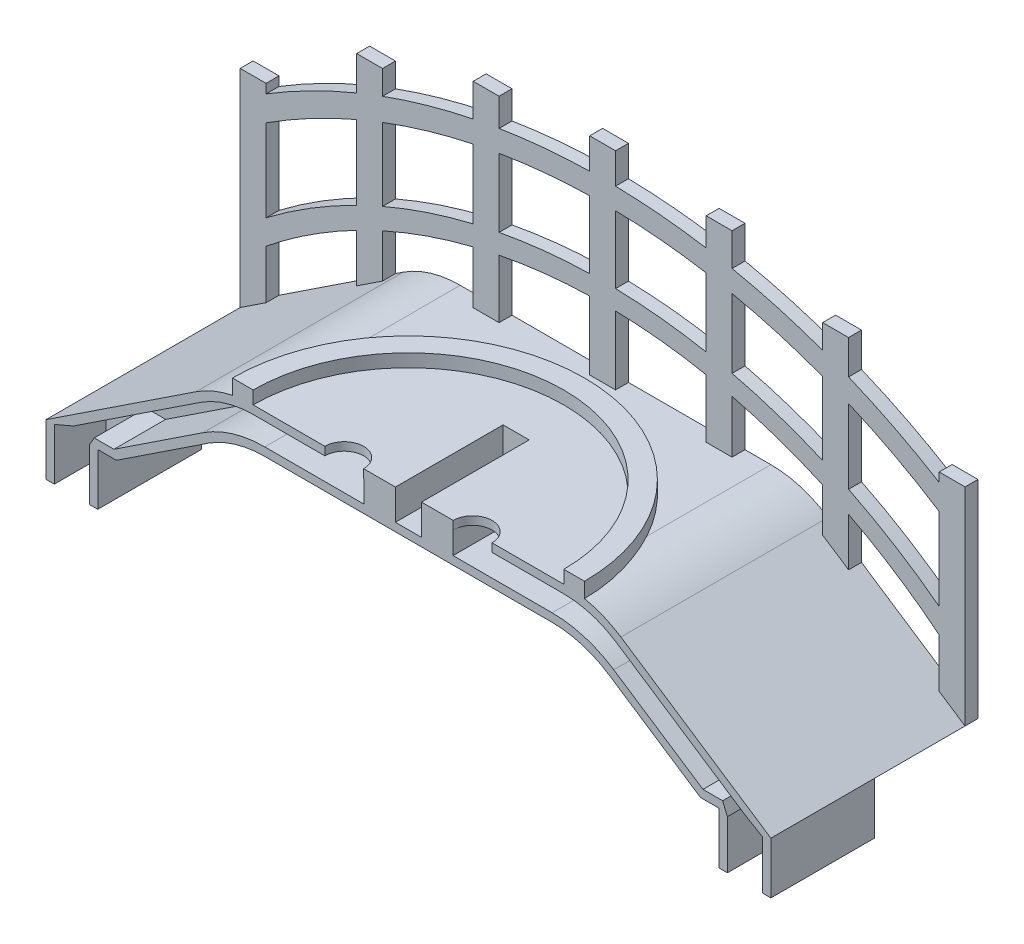
SolidWorks part; units mm, degrees
ref_plane "Front Plane" through (0, 0, 0) normal (0, 0, 1) x (1, 0, 0)
ref_plane "Top Plane" through (0, 0, 0) normal (0, 1, 0) x (1, 0, 0)
ref_plane "Right Plane" through (0, 0, 0) normal (1, 0, 0) x (0, 0, -1)
sketch "Sketch5" plane through (0, 0, 0) normal (0, 0, 1) x (1, 0, 0)
  line L0 (1.3132, -1.9864) -> (9.914, 3.6997)
  line L1 (12.7, 7.134) -> (31.75, 7.134)
  line L2 (0, 0) -> (9.198, 6.081)
  line L3 (35.252, 6.081) -> (44.45, 0)
  line L4 (0, 0) -> (10.7907, 0) construction
  line L5 (44.45, 0) -> (33.6593, 0) construction
  line L6 (13.416, 4.7527) -> (31.034, 4.7527)
  line L7 (34.536, 3.6997) -> (43.1368, -1.9864)
  line L8 (0, 0) -> (4.3178, 0)
  line L9 (44.45, 0) -> (40.1322, 0)
  line L10 (0, 0) -> (0, 9.525)
  line L11 (44.45, 0) -> (44.45, 9.525)
  line L12 (22.225, 7.134) -> (22.225, 16.659) construction
  line L13 (22.225, 7.134) -> (22.225, 3.959) construction
  line L14 (0, 0) -> (1.5875, 0)
  line L15 (0, 0) -> (0, 12.7)
  line L16 (0, 12.7) -> (1.5875, 12.7)
  line L17 (1.5875, 0) -> (1.5875, 12.7)
  line L18 (23.0187, 3.959) -> (21.4312, 3.959)
  line L19 (23.0187, 3.959) -> (23.0188, 19.834)
  line L20 (23.0188, 19.834) -> (21.4312, 19.834)
  line L21 (21.4312, 3.959) -> (21.4312, 19.834)
  line L22 (1.5875, 9.2118) -> (7.1438, 9.2118) construction
  line L23 (7.1437, 17.0604) -> (8.7312, 17.0604)
  line L24 (7.1437, 17.0604) -> (7.1438, 1.1854)
  line L25 (7.1438, 1.1854) -> (8.7313, 1.1854)
  line L26 (8.7312, 17.0604) -> (8.7313, 1.1854)
  line L27 (14.2875, 19.1598) -> (15.875, 19.1598)
  line L28 (14.2875, 19.1598) -> (14.2875, 3.2848)
  line L29 (14.2875, 3.2848) -> (15.875, 3.2848)
  line L30 (15.875, 19.1598) -> (15.875, 3.2848)
  line L31 (8.7313, 8.208) -> (14.2875, 8.208) construction
  line L32 (15.875, 13.1596) -> (21.4312, 13.1596) construction
  line L33 (7.9375, 17.0604) -> (7.9375, 13.8854) construction
  line L34 (15.0812, 19.1598) -> (15.0812, 15.9848) construction
  line L35 (44.45, 0) -> (40.1322, 0)
  line L36 (30.1625, 19.1598) -> (28.575, 19.1598)
  line L37 (30.1625, 19.1598) -> (30.1625, 3.2848)
  line L38 (28.575, 19.1598) -> (28.575, 3.2848)
  line L39 (30.1625, 3.2848) -> (28.575, 3.2848)
  line L40 (37.3062, 1.1854) -> (35.7187, 1.1854)
  line L41 (37.3062, 17.0604) -> (35.7187, 17.0604)
  line L42 (35.7187, 17.0604) -> (35.7187, 1.1854)
  line L43 (37.3062, 17.0604) -> (37.3062, 1.1854)
  line L44 (44.45, 12.7) -> (42.8625, 12.7)
  line L45 (44.45, 0) -> (44.45, 12.7)
  line L46 (44.45, 0) -> (44.45, 9.525)
  line L47 (42.8625, 0) -> (42.8625, 12.7)
  line L48 (11.5067, 4.7527) -> (32.9433, 4.7527) construction
  line L49 (32.9433, 4.7527) -> (43.1368, -1.9864) construction
  line L50 (10.7907, 7.134) -> (33.6593, 7.134) construction
  line L51 (33.6593, 7.134) -> (44.45, 0) construction
  line L52 (1.3132, -1.9864) -> (11.5067, 4.7527) construction
  line L53 (0, 0) -> (10.7907, 7.134) construction
  arc A0 (0, 9.525) -> (44.45, 9.525) centre (22.225, -21.5277) cw
  arc A1 (0, 11.1125) -> (44.45, 11.1125) centre (22.225, -21.5277) cw
  arc A2 (31.034, 4.7527) -> (34.536, 3.6997) centre (31.034, -1.5973) cw
  arc A3 (31.75, 7.134) -> (35.252, 6.081) centre (31.75, 0.784) cw
  arc A4 (9.914, 3.6997) -> (13.416, 4.7527) centre (13.416, -1.5973) cw
  arc A5 (12.7, 7.134) -> (9.198, 6.081) centre (12.7, 0.784) ccw
  point P65 (33.6593, 7.134)
  dimension "D12" = 6.35
  dimension "D2" = 19.05
  dimension "D1" = 44.45
  dimension "D3" = 2.3813
  dimension "D4" = 9.525
  dimension "D5" = 1.5875
  dimension "D6" = 12.7
  dimension "D7" = 1.5875
  dimension "D8" = 15.875
  dimension "D9" = 12.7
  dimension "D10" = 3.175
  dimension "D11" = 1.5875
extrude "Boss-Extrude1" add sketch "Sketch5" along normal blind 12.7 contours L25 L24 L2 L17 L8 L0 | L8 L17 L2 | L26 L2 L24 L25 L0 | L28 A5 L2 L26 L0 A4 | L1 A5 L28 A4 L6 L30 | L1 L30 L6 L21 | L21 L6 L19 L1 | L38 L1 L19 L6 | A3 L1 L38 L6 A2 L37 | A3 L37 A2 L7 L42 L3 | L43 L3 L42 L7 L40 | L35 L47 L3 L43 L40 L7 | L47 L9 L3 region at (4.7092, 1.8379, 0) region at (7.9375, 3.8203, 0) region at (1.0583, 0.3498, 0) region at (11.4024, 5.4948, 0) region at (15.0812, 5.9433, 0) region at (18.6531, 5.9433, 0) region at (22.225, 5.9433, 0) region at (25.7969, 5.9433, 0) region at (29.3688, 5.9433, 0) region at (33.0476, 5.4948, 0) region at (36.5125, 3.8203, 0) region at (39.7408, 1.8379, 0) region at (43.3917, 0.3498, 0)
extrude "Boss-Extrude2" add sketch "Sketch5<4>" along normal blind 0.7937 separate body contours A1 L15 A0 L17 | A1 L17 A0 L24 | A1 L24 A0 L26 | A1 L26 A0 L28 | A1 L28 A0 L30 | A1 L30 A0 L21 | A1 L21 A0 L19 | A1 L19 A0 L38 | A1 L38 A0 L37 | A1 L37 A0 L42 | A1 L42 A0 L43 | A1 L43 A0 L47 | A1 L47 A0 L45 region at (4.3267, 12.8905, 0) region at (7.9352, 14.5811, 0) region at (0.7895, 10.851, 0) region at (11.4895, 15.7587, 0) region at (15.0802, 16.6439, 0) region at (18.647, 17.111, 0) region at (22.225, 17.3071, 0) region at (25.803, 17.111, 0) region at (29.3698, 16.6439, 0) region at (32.9605, 15.7587, 0) region at (36.5148, 14.5811, 0) region at (40.1233, 12.8905, 0) region at (43.6605, 10.851, 0)
sketch "Sketch5<4>" plane through (0, 0, 0) normal (0, 0, 1) x (1, 0, 0) same geometry as "Sketch5"
extrude "Boss-Extrude6" add sketch "Sketch5<7>" along normal blind 0.7937 contours L15 A1 L17 L16 | A0 L10 L2 L17 | A1 L15 A0 L17 | A0 L24 L2 L26 | L24 A1 L26 L23 | L26 L2 L24 L0 | L26 L0 L24 L25 | A1 L24 A0 L26 | L28 A1 L30 L27 | A1 L28 A0 L30 | A0 L28 L1 L30 | L30 L1 L28 L6 | L30 L6 L28 L29 | L21 L18 L19 L6 | L21 L6 L19 L1 | A0 L21 L1 L19 | L21 A1 L19 L20 | A1 L21 A0 L19 | L38 A1 L37 L36 | A0 L38 L1 L37 | L1 L38 L6 L37 | L39 L37 L6 L38 | L43 L7 L42 L40 | L43 L3 L42 L7 | A0 L42 L3 L43 | A1 L42 A0 L43 | L42 A1 L43 L41 | L47 A1 L45 L44 | A1 L47 A0 L45 | A0 L47 L3 L11 | L47 L9 L3 region at (7.9375, 3.8203, 0) region at (8.0525, 1.8272, 0) region at (7.9312, 9.5615, 0) region at (0.7941, 5.2992, 0) region at (7.9352, 14.5811, 0) region at (0.7895, 10.851, 0) region at (7.8917, 16.1623, 0) region at (0.6663, 12.1261, 0) region at (15.0812, 5.9433, 0) region at (15.0812, 4.0188, 0) region at (15.0858, 11.5584, 0) region at (15.0802, 16.6439, 0) region at (15.0604, 18.2312, 0) region at (22.225, 5.9433, 0) region at (22.225, 4.3558, 0) region at (22.225, 11.8951, 0) region at (22.225, 17.3071, 0) region at (22.225, 18.896, 0) region at (29.3688, 5.9433, 0) region at (29.3688, 4.0188, 0) region at (29.3642, 11.5584, 0) region at (29.3896, 18.2312, 0) region at (36.5188, 9.5615, 0) region at (36.5148, 14.5811, 0) region at (36.5583, 16.1623, 0) region at (36.5125, 3.8203, 0) region at (36.3975, 1.8272, 0) region at (43.6559, 5.2992, 0) region at (43.6605, 10.851, 0) region at (43.7837, 12.1261, 0) region at (43.3917, 0.3498, 0)
sketch "Sketch5<7>" plane through (0, 0, 0) normal (0, 0, 1) x (1, 0, 0) same geometry as "Sketch5"
sketch "Sketch6" plane through (0, 0, 0) normal (0, 0, -1) x (-1, 0, 0)
  line L0 (-44.45, 0) -> (-44.45, 12.7) construction
  line L1 (0, 0) -> (0, 12.7) construction
  line L2 (-44.45, 4.2704) -> (-44.45, 2.6829)
  line L3 (0, 2.6829) -> (0, 4.2704)
  arc A0 (-44.45, 4.2704) -> (0, 4.2704) centre (-22.225, -21.5277) cw
  arc A1 (-44.45, 2.6829) -> (0, 2.6829) centre (-22.225, -21.5277) cw
  arc A2 (-23.0187, 16.6507) -> (-28.575, 16.1273) centre (-22.225, -21.5277) ccw construction
  dimension "D1" = 1.5875
extrude "Boss-Extrude7" add sketch "Sketch6" against normal blind 0.7937
sketch "Sketch7" plane through (0, 0, 12.7) normal (0, 0, 1) x (1, 0, 0)
  line L0 (22.225, 7.134) -> (12.7, 7.134)
  line L1 (12.7, 7.134) -> (31.75, 7.134) construction
  line L2 (12.7, 7.134) -> (12.7, 6.626)
  line L3 (13.416, 4.7527) -> (31.034, 4.7527) construction
  line L4 (12.7, 6.626) -> (31.75, 6.626)
  line L5 (12.7, 6.626) -> (12.7, 5.2607)
  line L6 (12.7, 5.2607) -> (31.75, 5.2607)
  line L7 (31.75, 6.626) -> (31.75, 5.2607)
  line L20 (1.6895, 0.508) -> (4.1651, 0.508)
  line L21 (4.1651, 0.508) -> (9.6338, 4.1235)
  line L22 (9.4782, 5.6572) -> (1.6895, 0.508)
  line L23 (1.6895, 0.508) -> (4.1651, 0.508)
  line L24 (4.1651, 0.508) -> (9.6338, 4.1235)
  line L25 (9.4782, 5.6572) -> (1.6895, 0.508)
  line L37 (34.8162, 4.1235) -> (40.2849, 0.508)
  line L38 (40.2849, 0.508) -> (42.7605, 0.508)
  line L39 (42.7605, 0.508) -> (34.9718, 5.6572)
  line L40 (34.8162, 4.1235) -> (40.2849, 0.508)
  line L41 (40.2849, 0.508) -> (42.7605, 0.508)
  line L42 (42.7605, 0.508) -> (34.9718, 5.6572)
  arc A8 (13.416, 5.2607) -> (9.6338, 4.1235) centre (13.416, -1.5973) ccw
  arc A9 (12.7, 6.626) -> (9.4782, 5.6572) centre (12.7, 0.784) ccw
  arc A10 (13.416, 5.2607) -> (9.6338, 4.1235) centre (13.416, -1.5973) ccw
  arc A11 (12.7, 6.626) -> (9.4782, 5.6572) centre (12.7, 0.784) ccw
  arc A17 (34.8162, 4.1235) -> (31.034, 5.2607) centre (31.034, -1.5973) ccw
  arc A18 (34.9718, 5.6572) -> (31.75, 6.626) centre (31.75, 0.784) ccw
  arc A19 (34.8162, 4.1235) -> (31.034, 5.2607) centre (31.034, -1.5973) ccw
  arc A20 (34.9718, 5.6572) -> (31.75, 6.626) centre (31.75, 0.784) ccw
  dimension "D1" = 9.525
  dimension "D2" = 0.508
  dimension "D3" = 0.508
  dimension "D4" = 19.05
  dimension "D5" = 0.508
  dimension "D6" = 0.508
extrude "Cut-Extrude1" cut sketch "Sketch7" against normal blind 9.525 contours L7 L4 L5 L6 region at (22.225, 5.9433, 12.7)
sketch "Sketch8" plane through (0, 7.134, 0) normal (0, 1, 0) x (1, 0, 0)
  line L0 (12.7, -12.7) -> (31.75, -12.7) construction
  line L1 (18.288, -12.7) -> (12.7, -12.7)
  line L2 (26.162, -12.7) -> (31.75, -12.7)
  line L4 (23.0251, -19.304) -> (21.4249, -19.304)
  line L5 (23.0251, -19.304) -> (23.0251, -6.096)
  line L6 (23.0251, -6.096) -> (21.4249, -6.096)
  line L7 (21.4249, -19.304) -> (21.4249, -6.096)
  line L8 (23.0251, -19.304) -> (21.4249, -6.096) construction
  line L9 (23.0251, -6.096) -> (21.4249, -19.304) construction
  circle A0 centre (18.288, -12.7) radius 1.1906
  circle A1 centre (26.162, -12.7) radius 1.1906
  point P8 (22.225, -12.7)
  line M5 (12.7, -12.7) -> (31.75, -12.7)
  dimension "D1" = 2.3813
  dimension "D2" = 2.3813
  dimension "D3" = 5.588
  dimension "D4" = 1.6002
  dimension "D5" = 13.208
extrude "Cut-Extrude2" cut sketch "Sketch8" against normal blind 1.397 contours A0 L1 M5 | A1 M5 | L7 L5 L6 M5 region at (18.288, 7.134, 12.1947) region at (26.162, 7.134, 12.1947) region at (22.225, 7.134, 9.398)
sketch "Sketch10" plane through (0, 5.2607, 0) normal (0, 1, 0) x (1, 0, 0)
  line L0 (12.7, -12.7) -> (31.75, -12.7) construction
  line L1 (19.4888, -19.9033) -> (24.9612, -19.9033)
  line L2 (19.4888, -19.9033) -> (19.4888, -5.4967)
  line L3 (19.4888, -5.4967) -> (24.9612, -5.4967)
  line L4 (24.9612, -19.9033) -> (24.9612, -5.4967)
  line L5 (19.4888, -19.9033) -> (24.9612, -5.4967) construction
  line L6 (19.4888, -5.4967) -> (24.9612, -19.9033) construction
  line L7 (24.9612, -12.7) -> (19.4888, -12.7)
  line L8 (23.0251, -19.304) -> (21.4249, -19.304)
  line L9 (23.0251, -19.304) -> (23.0251, -6.096)
  line L10 (23.0251, -6.096) -> (21.4249, -6.096)
  line L11 (21.4249, -19.304) -> (21.4249, -6.096)
  line L12 (23.0251, -19.304) -> (21.4249, -6.096) construction
  line L13 (23.0251, -6.096) -> (21.4249, -19.304) construction
  line L14 (19.4786, -12.7) -> (21.4249, -12.7) construction
  point P0 (22.225, -12.7)
  point P7 (22.225, -12.7)
  point P15 (19.4888, -12.7)
  line M1 (12.7, -12.7) -> (31.75, -12.7)
extrude "Boss-Extrude8" add sketch "Sketch10" along normal blind 1.397 contours L11 L10 L9 L7 L4 L3 L2 M1 region at (19.5792, 5.2607, 9.0984)
sketch "Sketch11" plane through (0, 7.134, 0) normal (0, 1, 0) x (1, 0, 0)
  line L0 (21.4249, -12.7) -> (23.0251, -12.7) construction
  line L1 (11.43, -12.7) -> (33.02, -12.7)
  circle A0 centre (22.225, -12.7) radius 9.525
  circle A1 centre (22.225, -12.7) radius 10.795
  line M9 (31.75, -12.7) -> (31.75, 0)
  line M19 (12.7, 0) -> (12.7, -12.7)
  dimension "D1" = 19.05
  dimension "D2" = 21.59
extrude "Boss-Extrude9" add sketch "Sketch11" along normal blind 0.7937 and the other way blind 0.254 contours A1 A0 M9 M19 | A1 L1 M19 | L1 A1 M9 region at (12.1893, 7.134, 10.7791) region at (12.919, 7.134, 10.16) region at (32.2607, 7.134, 10.7791)
sketch "Sketch12" plane through (0, 0, 0) normal (0, -1, 0) x (1, 0, 0)
  line L1 (0, 12.7) -> (3.175, 12.7)
  line L2 (0, 12.7) -> (0, 6.35)
  line L3 (0, 6.35) -> (3.175, 6.35)
  line L4 (3.175, 12.7) -> (3.175, 6.35)
  line L5 (44.45, 12.7) -> (41.275, 12.7)
  line L6 (44.45, 12.7) -> (44.45, 6.35)
  line L7 (44.45, 6.35) -> (41.275, 6.35)
  line L8 (41.275, 12.7) -> (41.275, 6.35)
  dimension "D1" = 3.175
  dimension "D2" = 6.35
  dimension "D3" = 6.35
  dimension "D4" = 3.175
extrude "Boss-Extrude10" add sketch "Sketch12" along normal blind 3.175
sketch "Sketch14" plane through (0, 0, 12.7) normal (0, 0, 1) x (1, 0, 0)
extrude "Cut-Extrude3" cut sketch "Sketch7<4>" against normal blind 3.175 contours L5 A11 L25 L23 L24 A10 L6 | L42 A20 L7 L6 A19 L40 L41 region at (7.7102, 3.5955, 12.7) region at (36.7398, 3.5955, 12.7)
sketch "Sketch7<4>" plane through (0, 0, 12.7) normal (0, 0, 1) x (1, 0, 0) same geometry as "Sketch7"
sketch "Sketch15" plane through (0, 0, 12.7) normal (0, 0, 1) x (1, 0, 0)
  line L0 (1.6895, 0.508) -> (0.508, 0)
  line L1 (0.508, 0) -> (0.508, -3.175)
  line L2 (3.175, -3.175) -> (0, -3.175) construction
  line L3 (2.9595, 0.508) -> (2.667, 0)
  line L4 (2.667, 0) -> (2.667, -3.175)
  line L5 (42.7605, 0.508) -> (43.942, -0.1943)
  line L6 (43.942, -0.1943) -> (43.942, -3.175)
  line L7 (44.45, -3.175) -> (41.275, -3.175) construction
  line L8 (41.4905, 0.508) -> (41.783, -0.1943)
  line L9 (40.2849, 0.508) -> (42.7605, 0.508) construction
  line L10 (41.783, -0.1943) -> (41.783, -3.175)
  line L11 (41.783, -3.175) -> (43.942, -3.175)
  line L12 (0.508, -3.175) -> (2.667, -3.175)
  line L13 (0, -3.175) -> (0, 0) construction
  line L14 (3.175, -3.175) -> (3.175, 0) construction
  line L16 (44.45, -3.175) -> (44.45, 0) construction
  line L17 (41.275, -3.175) -> (41.275, 0) construction
  line L18 (1.6895, 0.508) -> (4.1651, 0.508) construction
  line L19 (1.6895, 0.508) -> (2.9595, 0.508)
  line L20 (41.4905, 0.508) -> (42.7605, 0.508)
  dimension "D1" = 0.508
  dimension "D2" = 0.508
  dimension "D3" = 0.508
  dimension "D4" = 0.508
  dimension "D5" = 1.27
  dimension "D6" = 1.27
extrude "Cut-Extrude4" cut sketch "Sketch15" against normal blind 3.175
sketch "Sketch16" plane through (0, 7.134, 0) normal (0, 1, 0) x (1, 0, 0)
  line L0 (13.416, -12.7) -> (19.4888, -12.7) construction
  line L1 (21.4249, -6.096) -> (16.6624, -6.096)
  line L2 (21.4249, -6.096) -> (21.4249, -12.7)
  line L3 (21.4249, -12.7) -> (16.6624, -12.7)
  line L4 (16.6624, -6.096) -> (16.6624, -12.7)
  dimension "D1" = 4.7625
